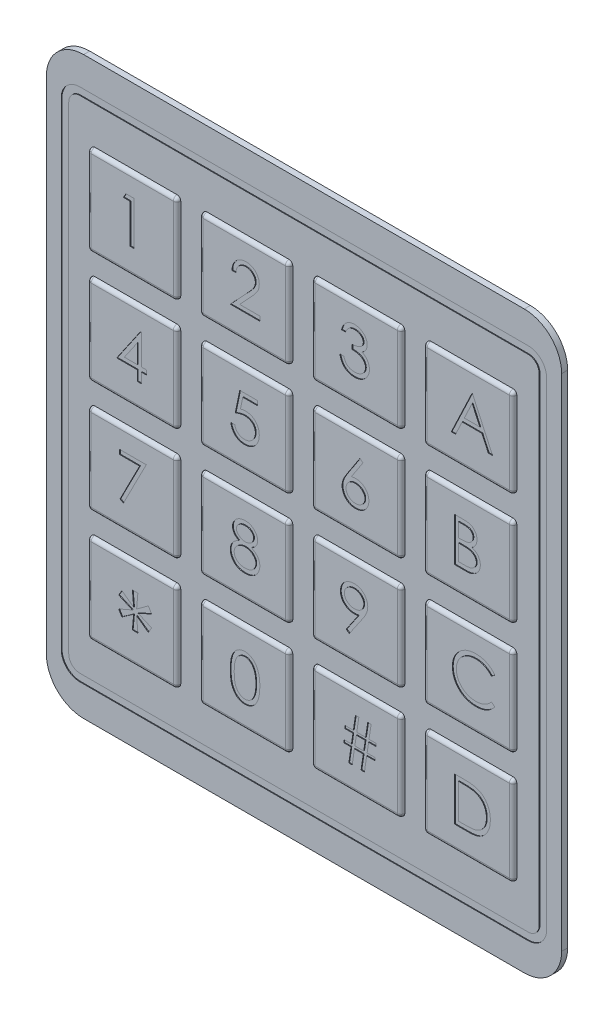
SolidWorks part; units mm, degrees
ref_plane "Alzado" through (0, 0, 0) normal (0, 0, 1) x (1, 0, 0)
ref_plane "Planta" through (0, 0, 0) normal (0, 1, 0) x (1, 0, 0)
ref_plane "Vista lateral" through (0, 0, 0) normal (1, 0, 0) x (0, 0, -1)
sketch "Croquis1" plane through (0, 0, 0) normal (0, 0, 1) x (1, 0, 0)
  line L1 (-34.5, 38.5) -> (34.5, 38.5)
  line L2 (-34.5, 38.5) -> (-34.5, -38.5)
  line L3 (-34.5, -38.5) -> (34.5, -38.5)
  line L4 (34.5, 38.5) -> (34.5, -38.5)
  point P4 (0, 38.5)
  point P6 (-34.5, 0)
  dimension "D1" = 77
  dimension "D2" = 69
extrude "Saliente-Extruir1" add sketch "Croquis1" along normal blind 0.81
fillet "Redondeo1" radius 5 4 edges at (-34.5, -38.5, 0.405) (34.5, -38.5, 0.405) (-34.5, 38.5, 0.405) (34.5, 38.5, 0.405)
sketch "Croquis4" plane through (0, 0, 0.81) normal (0, 0, 1) x (1, 0, 0)
  line L0 (-34.5, 33.5) -> (-34.5, -33.5) construction
  line L1 (-28.5, 28.5) -> (-16.5, 28.5)
  line L2 (-28.5, 28.5) -> (-28.5, 16.5)
  line L3 (-28.5, 16.5) -> (-16.5, 16.5)
  line L4 (-16.5, 28.5) -> (-16.5, 16.5)
  line L5 (29.5, 38.5) -> (-29.5, 38.5) construction
  dimension "D1" = 12
  dimension "D2" = 6
  dimension "D3" = 10
extrude "Saliente-Extruir2" add sketch "Croquis4" along normal blind 0.5
fillet "Redondeo2" radius 0.5 4 edges at (-22.5, 28.5, 1.31) (-16.5, 22.5, 1.31) (-22.5, 16.5, 1.31) (-28.5, 22.5, 1.31)
pattern_linear "MatrizL1" count 4 spacing 15 along (1, 0, 0) count 4 spacing 15 along (0, -1, 0) of "Saliente-Extruir2", "Redondeo2"
sketch "Croquis5" plane through (0, 0, 0.81) normal (0, 0, 1) x (1, 0, 0)
  line L0 (-34.5, 33.5) -> (-34.5, -33.5) construction
  line L1 (-30, 34.5) -> (30, 34.5)
  line L2 (-32.5, 32) -> (-32.5, -32)
  line L3 (-30, -34.5) -> (30, -34.5)
  line L4 (32.5, 32) -> (32.5, -32)
  line L5 (34.5, -33.5) -> (34.5, 33.5) construction
  line L6 (29.5, 38.5) -> (-29.5, 38.5) construction
  line L7 (-29.5, -38.5) -> (29.5, -38.5) construction
  line L8 (-30, 33.5) -> (30, 33.5)
  line L9 (31.5, 32) -> (31.5, -32)
  line L10 (-30, -33.5) -> (30, -33.5)
  line L11 (-31.5, 32) -> (-31.5, -32)
  arc A0 (-32.5, -32) -> (-30, -34.5) centre (-30, -32) ccw
  arc A1 (32.5, -32) -> (30, -34.5) centre (30, -32) cw
  arc A2 (32.5, 32) -> (30, 34.5) centre (30, 32) ccw
  arc A3 (-30, 34.5) -> (-32.5, 32) centre (-30, 32) ccw
  arc A4 (31.5, 32) -> (30, 33.5) centre (30, 32) ccw
  arc A5 (31.5, -32) -> (30, -33.5) centre (30, -32) cw
  arc A6 (-31.5, -32) -> (-30, -33.5) centre (-30, -32) ccw
  arc A7 (-30, 33.5) -> (-31.5, 32) centre (-30, 32) ccw
  dimension "D5" = 2.5
  dimension "D1" = 2
  dimension "D2" = 2
  dimension "D3" = 4
  dimension "D4" = 4
  dimension "D6" = 1
extrude "Cortar-Extruir1" cut sketch "Croquis5" against normal blind 0.1
sketch "Croquis6" plane through (0, 0, 1.31) normal (0, 0, 1) x (1, 0, 0)
  text T0 "1" font "Century Gothic" height in points 22
  text T1 "2" font "Century Gothic" height in points 22
  text T2 "3" font "Century Gothic" height in points 22
  text T3 "A" font "Century Gothic" height in points 22
  text T4 "B" font "Century Gothic" height in points 22
  text T5 "C" font "Century Gothic" height in points 22
  text T6 "D" font "Century Gothic" height in points 22
  text T7 "#" font "Century Gothic" height in points 22
  text T8 "0" font "Century Gothic" height in points 22
  text T9 "*" font "Century Gothic" height in points 36
  text T10 "4" font "Century Gothic" height in points 22
  text T11 "5" font "Century Gothic" height in points 22
  text T12 "6" font "Century Gothic" height in points 22
  text T13 "7" font "Century Gothic" height in points 22
  text T14 "8" font "Century Gothic" height in points 22
  text T15 "9" font "Century Gothic" height in points 22
extrude "Cortar-Extruir2" cut sketch "Croquis6" against normal blind 0.1
